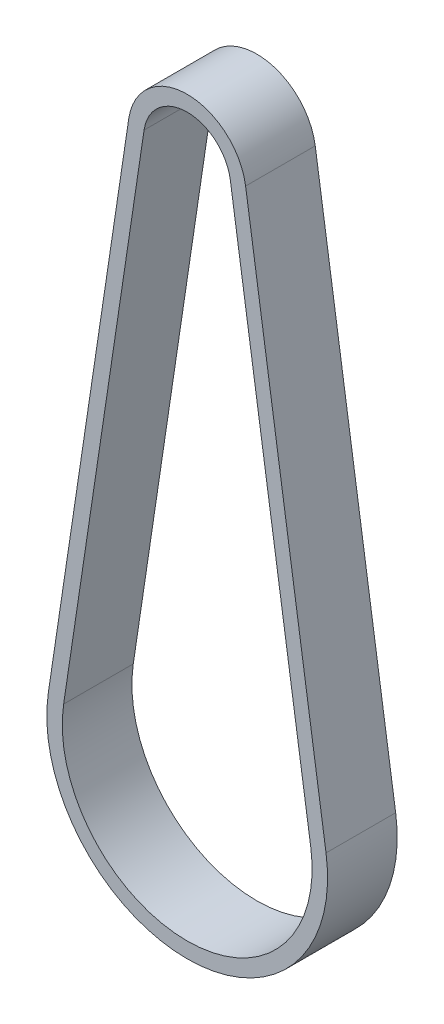
SolidWorks part; units mm, degrees
material "Rubber"
ref_plane "Front Plane" through (0, 0, 0) normal (0, 0, 1) x (1, 0, 0)
ref_plane "Top Plane" through (0, 0, 0) normal (0, 1, 0) x (1, 0, 0)
ref_plane "Right Plane" through (0, 0, 0) normal (1, 0, 0) x (0, 0, -1)
sketch "Sketch1" plane through (0, 0, 0) normal (0, 0, 1) x (1, 0, 0)
  line L0 (-7.5509, 1.1302) -> (-17.9451, -68.314)
  line L1 (7.5509, 1.1302) -> (17.9451, -68.314)
  arc A0 (7.5509, 1.1302) -> (-7.5509, 1.1302) centre (0, 0) ccw
  arc A1 (-17.9451, -68.314) -> (17.9451, -68.314) centre (0, -71) ccw
  dimension "D1" = 15.27
  dimension "D2" = 36.29
  dimension "D3" = 71
extrude "Extrude-Thin1" add sketch "Sketch1" along normal mid plane 9 thin thin type one direction reverse wall 2
